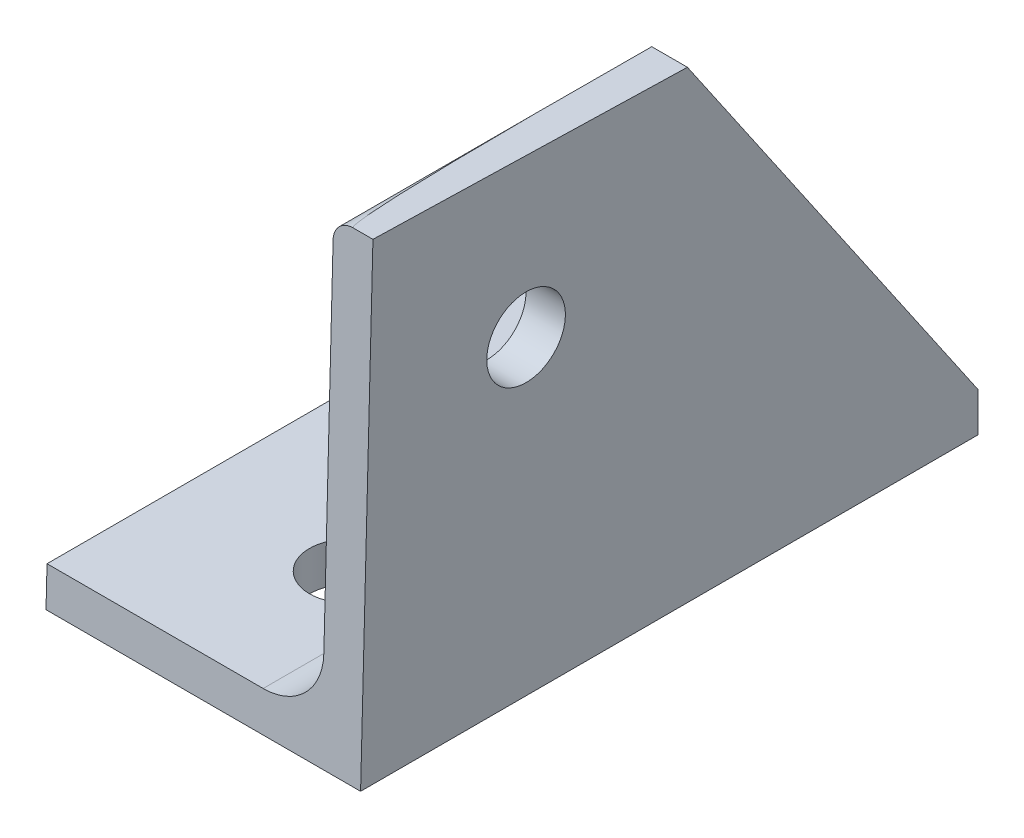
SolidWorks part; units mm, degrees
ref_plane "Front Plane" through (0, 0, 0) normal (0, 0, 1) x (1, 0, 0)
ref_plane "Top Plane" through (0, 0, 0) normal (0, 1, 0) x (1, 0, 0)
ref_plane "Right Plane" through (0, 0, 0) normal (1, 0, 0) x (0, 0, -1)
sketch "Sketch0" plane through (0, 0, 0) normal (0, 0, 1) x (1, 0, 0)
  line L0 (-19.05, -19.05) -> (19.05, -19.05)
  line L1 (19.05, -19.05) -> (19.05, 19.05)
  line L2 (19.05, 0) -> (0, 0) construction
  line L3 (0, 0) -> (0, -19.05) construction
  line L4 (15.875, -11.0998) -> (15.875, 19.05) construction
  line L5 (11.0998, -15.875) -> (-19.05, -15.875) construction
  arc A0 (15.875, -11.0998) -> (11.0998, -15.875) centre (11.0998, -11.0998) cw
  point P3 (14.4764, -14.4764)
  dimension "Inside Corner Radius" = 4.7752
  dimension "Outside Height" = 38.1
  dimension "Inside Height" = 34.925
  dimension "Inside Width" = 34.925
  dimension "Wall Thickness" = 3.175
  dimension "D1" = 3.175
  dimension "Outside Width" = 38.1
sketch "Sketch1" plane through (0, 0, 0) normal (1, 0, 0) x (0, 0, -1)
  line L0 (25.4, 0) -> (-25.4, 0)
  point P4 (0, 0)
  dimension "Length" = 50.8
sketch "Sketch2" plane through (0, 0, 0) normal (0, 0, 1) x (1, 0, 0)
  line L0 (-19.05, -19.05) -> (19.05, -19.05)
  line L1 (19.05, -19.05) -> (19.05, 19.05)
  line L2 (19.05, 19.05) -> (15.875, 19.05) construction
  line L3 (15.875, 17.4625) -> (15.875, -11.0998)
  line L4 (11.0998, -15.875) -> (-17.4625, -15.875)
  line L5 (-19.05, -19.05) -> (-19.05, -15.875) construction
  line L6 (17.4625, 19.05) -> (19.05, 19.05)
  line L7 (-19.05, -17.4625) -> (-19.05, -19.05)
  line L8 (19.05, 0) -> (0, 0) construction
  line L9 (0, 0) -> (0, -19.05) construction
  arc A0 (15.875, 17.4625) -> (17.4625, 19.05) centre (17.4625, 17.4625) cw
  arc A1 (-19.05, -17.4625) -> (-17.4625, -15.875) centre (-17.4625, -17.4625) cw
  arc A2 (15.875, -11.0998) -> (11.0998, -15.875) centre (11.0998, -11.0998) cw
  dimension "Inside Radius" = 4.7752
  dimension "Height" = 38.1
  dimension "Width" = 38.1
  dimension "Thickness" = 3.175
extrude "Boss-Extrude1" add sketch "Sketch2" along normal mid plane 50.8
sketch "Break Locations" plane through (0, 0, 0) normal (1, 0, 0) x (0, 0, -1)
  line L0 (13.462, 0) -> (-13.462, 0)
  line L1 (-25.4, -19.05) -> (-25.4, 19.05) construction
  line L2 (25.4, -19.05) -> (25.4, 19.05) construction
  point P0 (6.985, 0)
  point P1 (-6.985, 0)
  point P10 (0, 0)
  point P11 (-13.462, 0)
  point P13 (13.462, 0)
  dimension "D1" = 32.385
  dimension "D2" = 32.385
  dimension "D3" = 38.862
sketch "Sketch3" plane through (0, -19.05, 0) normal (0, -1, 0) x (1, 0, 0)
  line L0 (19.05, 25.4) -> (6.35, 25.4) construction
  line L1 (-19.05, 25.4) -> (19.05, 25.4) construction
  line L2 (6.35, 25.4) -> (6.35, 12.7) construction
  line L3 (6.35, 12.7) -> (6.35, -12.7) construction
  line L4 (-19.05, 25.4) -> (-6.35, 25.4)
  line L5 (-6.35, 25.4) -> (-6.35, -25.4)
  line L6 (-19.05, -25.4) -> (19.05, -25.4) construction
  line L7 (-6.35, -25.4) -> (-19.05, -25.4)
  line L8 (-19.05, -25.4) -> (-19.05, 25.4)
  circle A0 centre (6.35, 12.7) radius 3.175
  circle A1 centre (6.35, -12.7) radius 3.175
  dimension "D4" = 12.7
  dimension "D1" = 12.7
  dimension "D2" = 12.7
  dimension "D3" = 25.4
extrude "Cut-Extrude1" cut sketch "Sketch3" against normal through all
sketch "Sketch12" plane through (19.05, 0, 0) normal (1, 0, 0) x (0, 0, -1)
  line L2 (-25.4, 19.05) -> (25.4, 19.05) construction
  line L3 (-25.4, -19.05) -> (25.4, -19.05) construction
  line L9 (0, 19.05) -> (0, -19.05) construction
  line L10 (25.4, -19.05) -> (-24.4495, -19.05)
  line L11 (25.4, -15.875) -> (25.4, -19.05)
  line L12 (1.9395, 18.3851) -> (25.4, -15.875)
  line L13 (-23.4518, 19.05) -> (1.9395, 18.3851)
  line L14 (-23.4518, 19.05) -> (-24.4495, -19.05)
extrude "Cut-Extrude2" cut sketch "Sketch12" against normal through all flip side to cut
sketch "Sketch13" plane through (19.05, 0, 0) normal (1, 0, 0) x (0, 0, -1)
  line L2 (-10.7562, 18.7176) -> (-11.0886, 6.0219) construction
  line L4 (1.9395, 18.3851) -> (-23.4518, 19.05) construction
  circle A2 centre (-11.0886, 6.0219) radius 3.175
extrude "Cut-Extrude3" cut sketch "Sketch13" against normal through all
equation "\"D1@Break Locations\" = .85 * \"Height@Sketch2\""
equation "\"D2@Break Locations\"=\"D1@Break Locations\""
equation "\"Thickness@Sketch2\"=\"wall thickness@sketch0\""
equation "\"Height@Sketch2\"=\"outside height@sketch0\""
equation "\"Width@Sketch2\"=\"outside width@sketch0\""
equation "\"Inside Radius@Sketch2\"=\"inside corner radius@sketch0\""
equation "\"Length@Boss-Extrude1\"=\"length@sketch1\""
equation "\"D3@Break Locations\"=\"D2@Break Locations\"*1.2"
equation "\"D1@Sketch0\"=\"Wall Thickness@Sketch0\""
